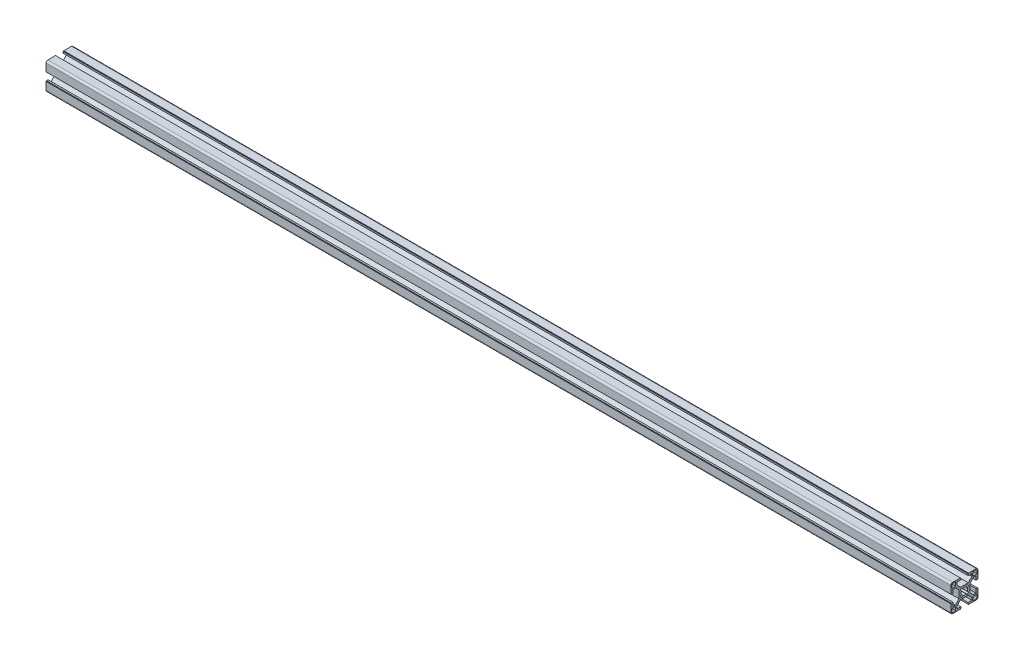
SolidWorks part; units mm, degrees
ref_plane "Front Plane" through (0, 0, 0) normal (0, 0, 1) x (1, 0, 0)
ref_plane "Top Plane" through (0, 0, 0) normal (0, 1, 0) x (1, 0, 0)
ref_plane "Right Plane" through (0, 0, 0) normal (1, 0, 0) x (0, 0, -1)
sketch "Sketch2" plane through (0, 0, 0) normal (1, 0, 0) x (0, 0, -1)
  line L0 (-13.85, -9.7) -> (-13.85, -12.85)
  line L1 (-12.85, -13.85) -> (-9.7, -13.85)
  line L2 (-9.7, -13.85) -> (-9.7, -9.7)
  line L3 (-9.7, -9.7) -> (-13.85, -9.7)
  line L4 (9.7, -13.85) -> (12.85, -13.85)
  line L5 (13.85, -12.85) -> (13.85, -9.7)
  line L6 (13.85, -9.7) -> (9.7, -9.7)
  line L7 (9.7, -9.7) -> (9.7, -13.85)
  line L8 (13.85, 9.7) -> (13.85, 12.85)
  line L9 (12.85, 13.85) -> (9.7, 13.85)
  line L10 (9.7, 13.85) -> (9.7, 9.7)
  line L11 (9.7, 9.7) -> (13.85, 9.7)
  line L12 (-9.7, 13.85) -> (-12.85, 13.85)
  line L13 (-13.85, 12.85) -> (-13.85, 9.7)
  line L14 (-13.85, 9.7) -> (-9.7, 9.7)
  line L15 (-9.7, 9.7) -> (-9.7, 13.85)
  line L16 (-3.2724, -1.6168) -> (-4.5905, -3.1877)
  line L17 (-4.5905, -3.1877) -> (-3.1877, -4.5905)
  line L18 (-3.1877, -4.5905) -> (-1.6168, -3.2724)
  line L19 (1.6168, -3.2724) -> (3.1877, -4.5905)
  line L20 (3.1877, -4.5905) -> (4.5905, -3.1877)
  line L21 (4.5905, -3.1877) -> (3.2724, -1.6168)
  line L22 (3.2724, 1.6168) -> (4.5905, 3.1877)
  line L23 (4.5905, 3.1877) -> (3.1877, 4.5905)
  line L24 (3.1877, 4.5905) -> (1.6168, 3.2724)
  line L25 (-1.6168, 3.2724) -> (-3.1877, 4.5905)
  line L26 (-3.1877, 4.5905) -> (-4.5905, 3.1877)
  line L27 (-4.5905, 3.1877) -> (-3.2724, 1.6168)
  line L28 (-6, 4.1969) -> (-10.0531, 8.25)
  line L29 (-10.0531, 8.25) -> (-12.8, 8.25)
  line L30 (-12.8, 8.25) -> (-12.8, 4.05)
  line L31 (-12.8, 4.05) -> (-14.5, 4.05)
  line L32 (-14.5, 4.05) -> (-14.5, 4.55)
  line L33 (-14.5, 4.55) -> (-15, 4.55)
  line L34 (-15, 4.55) -> (-15, 13)
  line L35 (-13, 15) -> (-4.55, 15)
  line L36 (-4.55, 15) -> (-4.55, 14.5)
  line L37 (-4.55, 14.5) -> (-4.05, 14.5)
  line L38 (-4.05, 14.5) -> (-4.05, 12.8)
  line L39 (-4.05, 12.8) -> (-8.25, 12.8)
  line L40 (-8.25, 12.8) -> (-8.25, 10.0531)
  line L41 (-8.25, 10.0531) -> (-4.1969, 6)
  line L42 (-4.1969, 6) -> (4.1969, 6)
  line L43 (4.1969, 6) -> (8.25, 10.0531)
  line L44 (8.25, 10.0531) -> (8.25, 12.8)
  line L45 (8.25, 12.8) -> (4.05, 12.8)
  line L46 (4.05, 12.8) -> (4.05, 14.5)
  line L47 (4.05, 14.5) -> (4.55, 14.5)
  line L48 (4.55, 14.5) -> (4.55, 15)
  line L49 (4.55, 15) -> (13, 15)
  line L50 (15, 13) -> (15, 4.55)
  line L51 (15, 4.55) -> (14.5, 4.55)
  line L52 (14.5, 4.55) -> (14.5, 4.05)
  line L53 (14.5, 4.05) -> (12.8, 4.05)
  line L54 (12.8, 4.05) -> (12.8, 8.25)
  line L55 (12.8, 8.25) -> (10.0531, 8.25)
  line L56 (10.0531, 8.25) -> (6, 4.1969)
  line L57 (6, 4.1969) -> (6, -4.1969)
  line L58 (6, -4.1969) -> (10.0531, -8.25)
  line L59 (10.0531, -8.25) -> (12.8, -8.25)
  line L60 (12.8, -8.25) -> (12.8, -4.05)
  line L61 (12.8, -4.05) -> (14.5, -4.05)
  line L62 (14.5, -4.05) -> (14.5, -4.55)
  line L63 (14.5, -4.55) -> (15, -4.55)
  line L64 (15, -4.55) -> (15, -13)
  line L65 (13, -15) -> (4.55, -15)
  line L66 (4.55, -15) -> (4.55, -14.5)
  line L67 (4.55, -14.5) -> (4.05, -14.5)
  line L68 (4.05, -14.5) -> (4.05, -12.8)
  line L69 (4.05, -12.8) -> (8.25, -12.8)
  line L70 (8.25, -12.8) -> (8.25, -10.0531)
  line L71 (8.25, -10.0531) -> (4.1969, -6)
  line L72 (4.1969, -6) -> (-4.1969, -6)
  line L73 (-4.1969, -6) -> (-8.25, -10.0531)
  line L74 (-8.25, -10.0531) -> (-8.25, -12.8)
  line L75 (-8.25, -12.8) -> (-4.05, -12.8)
  line L76 (-4.05, -12.8) -> (-4.05, -14.5)
  line L77 (-4.05, -14.5) -> (-4.55, -14.5)
  line L78 (-4.55, -14.5) -> (-4.55, -15)
  line L79 (-4.55, -15) -> (-13, -15)
  line L80 (-15, -13) -> (-15, -4.55)
  line L81 (-15, -4.55) -> (-14.5, -4.55)
  line L82 (-14.5, -4.55) -> (-14.5, -4.05)
  line L83 (-14.5, -4.05) -> (-12.8, -4.05)
  line L84 (-12.8, -4.05) -> (-12.8, -8.25)
  line L85 (-12.8, -8.25) -> (-10.0531, -8.25)
  line L86 (-10.0531, -8.25) -> (-6, -4.1969)
  line L87 (-6, -4.1969) -> (-6, 4.1969)
  arc A0 (-13.85, -12.85) -> (-12.85, -13.85) centre (-12.85, -12.85) ccw
  arc A1 (12.85, -13.85) -> (13.85, -12.85) centre (12.85, -12.85) ccw
  arc A2 (13.85, 12.85) -> (12.85, 13.85) centre (12.85, 12.85) ccw
  arc A3 (-12.85, 13.85) -> (-13.85, 12.85) centre (-12.85, 12.85) ccw
  arc A4 (-3.2724, 1.6168) -> (-3.2724, -1.6168) centre (0, 0) ccw
  arc A5 (-1.6168, -3.2724) -> (1.6168, -3.2724) centre (0, 0) ccw
  arc A6 (3.2724, -1.6168) -> (3.2724, 1.6168) centre (0, 0) ccw
  arc A7 (1.6168, 3.2724) -> (-1.6168, 3.2724) centre (0, 0) ccw
  arc A8 (-13, 15) -> (-15, 13) centre (-13, 13) ccw
  arc A9 (15, 13) -> (13, 15) centre (13, 13) ccw
  arc A10 (13, -15) -> (15, -13) centre (13, -13) ccw
  arc A11 (-15, -13) -> (-13, -15) centre (-13, -13) ccw
  point P109 (0, 0)
extrude "BR_Extrude" add sketch "Sketch2" along normal blind 500 and the other way blind 500
ref_axis "BR_Axis" through (-550, 0, 0) along (1, 0, 0)
